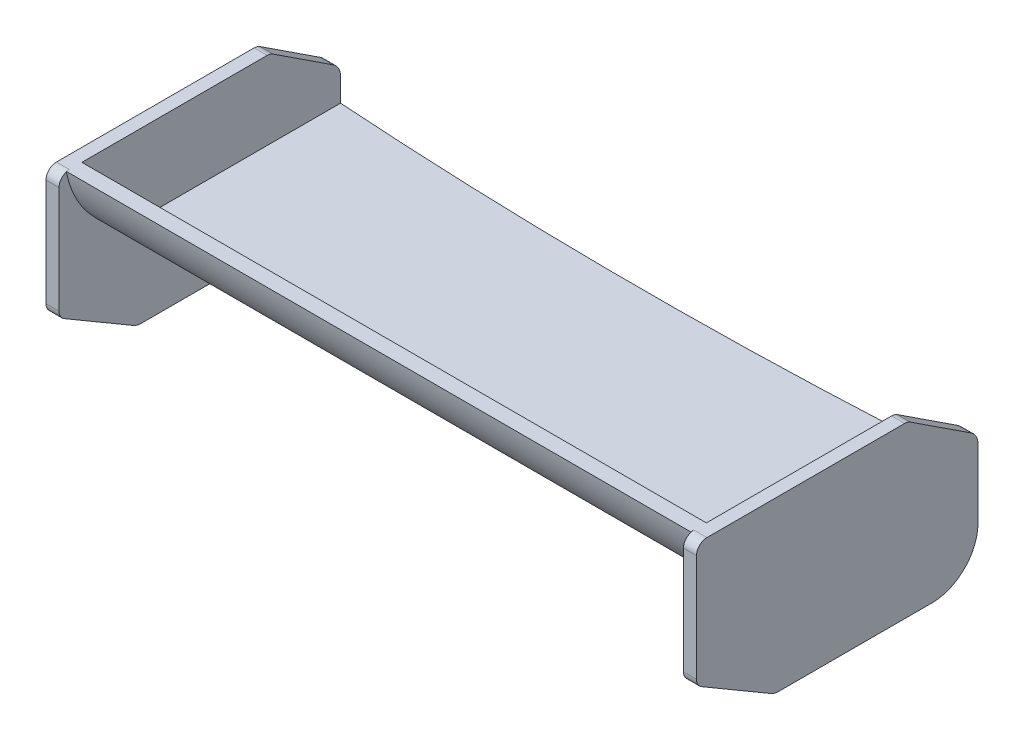
SolidWorks part; units mm, degrees
ref_plane "Alzado" through (0, 0, 0) normal (0, 0, 1) x (1, 0, 0)
ref_plane "Planta" through (0, 0, 0) normal (0, 1, 0) x (1, 0, 0)
ref_plane "Vista lateral" through (0, 0, 0) normal (1, 0, 0) x (0, 0, -1)
sketch "Croquis3" plane through (0, 0, 0) normal (0, 1, 0) x (1, 0, 0)
  line L1 (-60, 0) -> (-60, -35.6)
  line L2 (60, 0) -> (60, -35.6)
  line L3 (-60, -17.8) -> (60, -17.8) construction
  arc A0 (-60, 0) -> (60, 0) centre (0, 894.1246) ccw
  arc A1 (-60, -35.6) -> (60, -35.6) centre (0, 858.5246) ccw
  point P4 (0, 0)
  dimension "D1" = 120
  dimension "D2" = 35.6
extrude "Saliente-Extruir2" add sketch "Croquis3" along normal blind 2.5
ref_plane "Plano2" through (0, 0, 0) normal (1, 0, 0) x (0, 0, -1)
sketch "Croquis6" plane through (0, 2.5, 0) normal (0, 1, 0) x (1, 0, 0)
  line L1 (0, -37.6109) -> (0, -39.1109)
  line L2 (0, -1.375) -> (0, 1.375) construction
  line L3 (-60, -37.1) -> (-60, -52.7)
  line L4 (60, -37.1) -> (60, -52.7)
  arc A1 (-60, -52.7) -> (60, -52.7) centre (0, 841.4246) ccw
  arc A2 (-60, -37.1) -> (60, -37.1) centre (0, 857.0246) ccw
  dimension "D1" = 15.6
extrude "Saliente-Extruir3" add sketch "Croquis6" along normal blind 15 separate body contours A2 L3 A1 L4 region at (0, 2.5, 46.2409)
sketch "Croquis7" plane through (60, 0, 0) normal (1, 0, 0) x (0, 0, -1)
  line L0 (-52.7, 17.5) -> (-49.7, 17.5)
  line L1 (-37.1, 17.5) -> (-52.7, 17.5) construction
  line L2 (-37.1, 2.5) -> (-40.1, 2.5)
  line L3 (-37.1, 2.5) -> (-52.7, 2.5) construction
  line L4 (-49.7, 17.5) -> (-37.1, 17.5)
  line L5 (-37.1, 17.5) -> (-37.1, 2.5)
  line L6 (-52.7, 17.5) -> (-52.7, 2.5)
  line L7 (-52.7, 17.5) -> (-52.7, 2.5) construction
  line L8 (-52.7, 2.5) -> (-40.1, 2.5)
  arc A0 (-49.7, 17.5) -> (-37.1, 2.5) centre (-29.8357, 21.394) ccw
  arc A1 (-52.7, 17.5) -> (-40.1, 2.5) centre (-33.0482, 21.2155) ccw
  line M5 (-52.7, 2.5) -> (-37.1, 2.5)
  line M6 (-37.1, 2.5) -> (-37.1, 17.5)
  line M7 (-37.1, 17.5) -> (-52.7, 17.5)
  line M8 (-52.7, 17.5) -> (-52.7, 2.5)
extrude "Cortar-Extruir1" cut sketch "Croquis7" against normal blind 135 contours A0 M7 M6 | A1 M8 M5 region at (60, 6.4714, 49.2339) region at (60, 11.6756, 42.0524)
sketch "Croquis8" plane through (0, 17.5, 0) normal (0, 1, 0) x (1, 0, 0)
  line L0 (-60, -52.7) -> (60, -52.7)
  arc A0 (-60, -52.7) -> (60, -52.7) centre (0, 841.4246) ccw
extrude "Cortar-Extruir2" cut sketch "Croquis8" against normal blind 135
sketch "Croquis9" plane through (60, 0, 0) normal (1, 0, 0) x (0, 0, -1)
  line L1 (-54.0966, 15.5) -> (-54.0966, -5.0785)
  line L9 (-52.0966, 17.5) -> (-14.0966, 17.5)
  line L10 (0, 7.038) -> (0, -6.1372)
  line L12 (-13.0009, 17.1732) -> (-1.3565, 9.5477)
  line L14 (-38.3051, -15) -> (-8.8406, -15)
  line L15 (-53.1076, -6.8041) -> (-39.8217, -14.5884)
  arc A0 (-14.0966, 17.5) -> (-13.0009, 17.1732) centre (-14.0966, 15.5) cw
  arc A1 (-54.0966, 15.5) -> (-52.0966, 17.5) centre (-52.0966, 15.5) cw
  arc A3 (-38.3051, -15) -> (-39.8217, -14.5884) centre (-38.3051, -12) cw
  arc A4 (0, 7.038) -> (-1.3565, 9.5477) centre (-3, 7.038) ccw
  arc A6 (0, -6.1372) -> (-8.8851, -15) centre (-8.8629, -6.1372) cw
  arc A7 (-53.1076, -6.8041) -> (-54.0966, -5.0785) centre (-52.0966, -5.0785) cw
  point P7 (-35.6, 1.25)
  point P13 (0, 0.4504)
  point P20 (-52.7, 17.5)
  line M15 (-35.6, 0) -> (0, 0)
  line M16 (0, 0) -> (0, 2.5)
  line M17 (0, 2.5) -> (-35.6, 2.5)
  line M18 (-35.6, 2.5) -> (-35.6, 0)
  dimension "D1" = 2
  dimension "D2" = 3
  dimension "D3" = 2
extrude "Saliente-Extruir4" add sketch "Croquis9" along normal blind 2.5 contours A7 L15 A3 L14 A6 L10 A4 L12 A0 L9 A1 M15 M18 M17 | M18 M15 M16 M17 region at (60, 16.468, 53.0646) region at (60, 1.25, 17.8)
mirror "Simetría1" about plane through (0, 0, 0) normal (1, 0, 0) of "Saliente-Extruir4"
sketch "Croquis10" plane through (0, 2.5, 0) normal (0, 1, 0) x (1, 0, 0)
  line L2 (0, -2.0109) -> (0.75, -2.0106)
  line L3 (0.75, -2.0106) -> (0.75, -37.6106)
  line L4 (-0.75, -2.0106) -> (-0.75, -37.6106)
  line L7 (-33.55, -1.3826) -> (-33.55, -36.9826)
  line L8 (-32.05, -1.4376) -> (-32.05, -37.0376)
  line L11 (32.05, -1.4376) -> (32.05, -37.0376)
  line L12 (33.55, -1.3826) -> (33.55, -36.9826)
  arc A0 (-0.75, -2.0106) -> (0.75, -2.0106) centre (0, 894.1246) ccw
  arc A1 (-33.55, -1.3826) -> (-32.05, -1.4376) centre (0, 894.1246) ccw
  arc A2 (32.05, -1.4376) -> (33.55, -1.3826) centre (0, 894.1246) ccw
  arc A4 (-33.55, -36.9826) -> (-32.05, -37.0376) centre (0, 858.5246) ccw
  arc A5 (-0.75, -37.6106) -> (0.75, -37.6106) centre (0, 858.5246) ccw
  arc A6 (32.05, -37.0376) -> (33.55, -36.9826) centre (0, 858.5246) ccw
  point P10 (0, -2.0109)
  point P16 (0, -2.0109)
  point P22 (0.75, -2.0106)
  point P26 (0, -37.6109)
  point P29 (-0.75, -2.0112)
extrude "Saliente-Extruir5" add sketch "Croquis10" against normal blind 3.5 contours L8 A4 L7 A1 | A0 L4 A5 L3 | L12 A6 L11 A2
sketch "Croquis11" plane through (0, 0, 0) normal (0, -1, 0) x (1, 0, 0)
  line L0 (-32.05, 23.6109) -> (-32.05, 22.1109)
  line L2 (32.05, 1.4376) -> (32.05, 37.0376) construction
  line L3 (-32.05, 16.1109) -> (-32.05, 14.6109)
  line L5 (-32.05, 9.9109) -> (-32.05, 8.4109)
  line L6 (32.05, 9.9109) -> (32.05, 8.4109)
  line L7 (-32.05, 23.6109) -> (32.05, 23.6109)
  line L8 (-32.05, 22.1109) -> (32.05, 22.1109)
  line L9 (32.05, 16.1109) -> (32.05, 14.6109)
  line L10 (-32.05, 16.1109) -> (32.05, 16.1109)
  line L11 (32.05, 23.6109) -> (32.05, 22.1109)
  line L12 (-32.05, 14.6109) -> (32.05, 14.6109)
  line L13 (32.05, 1.4376) -> (32.05, 37.0376) construction
  line L14 (-60, 29.8109) -> (60, 29.8109)
  line L15 (-32.05, 9.9109) -> (32.05, 9.9109)
  line L16 (60, 38.3051) -> (60, 8.8406) construction
  line L17 (-32.05, 8.4109) -> (32.05, 8.4109)
  line L20 (-60, 28.3109) -> (60, 28.3109)
  line L21 (-60, 29.8109) -> (-60, 28.3109)
  line L22 (60, 29.8109) -> (60, 28.1162)
  point P5 (0, 29.8109)
  point P12 (0, 29.8109)
  point P13 (0, 28.3109)
  point P16 (0, 28.3109)
  point P28 (0, 16.1109)
  point P34 (0, 14.6109)
  point P38 (0, 9.9109)
  point P41 (0, 8.4109)
  line M27 (-0.75, 2.0106) -> (-0.75, 37.6106)
  line M29 (-32.05, 37.0376) -> (-32.05, 1.4376)
extrude "Saliente-Extruir6" add sketch "Croquis11" along normal blind 1 contours L12 L10 M29 M27 | L12 L9 L10 M27 | L8 L7 M29 M27 | L11 L7 L8 M27 | L17 L6 L15 L5 region at (-16.4, 0, 22.8609) region at (15.65, 0, 22.8609) region at (-16.4, 0, 15.3609) region at (15.65, 0, 15.3609)
sketch "Croquis12" plane through (0, 0, 0) normal (0, -1, 0) x (1, 0, 0)
  line L4 (-32.05, 9.9109) -> (-32.05, 8.4109)
  line L5 (-60, 29.8109) -> (-60, 28.3109)
  line L7 (-60, 28.3109) -> (60, 28.3109)
  line L8 (60, 35.6) -> (60, 0) construction
  line L9 (-60, 29.8109) -> (60, 29.8109)
  line L10 (60, 38.3051) -> (60, 8.8406) construction
  line L13 (60, 29.8109) -> (60, 28.3109)
  point P21 (-0.75, 28.3109)
  point P25 (-0.75, 29.8109)
extrude "Saliente-Extruir7" add sketch "Croquis12" along normal blind 1 contours L9 L13 L7 L5
sketch "Croquis13" plane through (0, 0, 0) normal (0, -1, 0) x (1, 0, 0)
  line L0 (0, 37.6109) -> (0, 2.4457)
  line L2 (33.55, 13.0109) -> (33.55, 11.5109)
  line L3 (33.55, 1.3826) -> (33.55, 28.3109) construction
  line L4 (33.55, 13.0109) -> (60, 13.0109)
  line L5 (60, 28.3109) -> (60, 0) construction
  line L6 (33.55, 11.5109) -> (60, 11.5109)
  line L7 (60, 38.3051) -> (60, 8.8406) construction
  line L8 (60, 13.0109) -> (60, 11.5109)
  line L9 (-60, 13.0109) -> (-60, 11.5109)
  line L10 (-33.55, 13.0109) -> (-33.55, 11.5109)
  line L11 (-33.55, 11.5109) -> (-60, 11.5109)
  line L12 (-33.55, 13.0109) -> (-60, 13.0109)
  arc A0 (0.75, 37.6106) -> (-0.75, 37.6106) centre (0, -858.5246) ccw construction
  point P11 (33.55, 12.2609)
  point P23 (-33.55, 12.2609)
extrude "Saliente-Extruir8" add sketch "Croquis13" along normal blind 1 contours L11 L9 L12 L10 | L4 L8 L6 L2
sketch "Croquis14" plane through (0, 0, 0) normal (0, -1, 0) x (1, 0, 0)
  line L0 (-50.7801, 28.3109) -> (-49.2801, 28.3109)
  line L1 (50.7801, 13.0109) -> (49.2801, 13.0109)
  line L2 (-50.7801, 13.0109) -> (-49.2801, 13.0109)
  line L3 (-33.55, 13.0109) -> (-60, 13.0109) construction
  line L4 (-60, 28.3109) -> (-33.55, 28.3109) construction
  line L5 (-49.2801, 28.3109) -> (-49.2801, 13.0109)
  line L6 (-33.55, 13.0109) -> (-60, 13.0109) construction
  line L7 (-50.7801, 28.3109) -> (-50.7801, 13.0109)
  line L8 (0, 37.6109) -> (0, 2.0109) construction
  line L9 (50.7801, 28.3109) -> (49.2801, 28.3109)
  line L10 (50.7801, 28.3109) -> (50.7801, 13.0109)
  line L11 (49.2801, 28.3109) -> (49.2801, 13.0109)
  arc A0 (0.75, 37.6106) -> (-0.75, 37.6106) centre (0, -858.5246) ccw construction
  arc A1 (0.75, 2.0106) -> (-0.75, 2.0106) centre (0, -894.1246) ccw construction
  point P12 (-50.0301, 28.3109)
extrude "Saliente-Extruir9" add sketch "Croquis14" along normal blind 1
sketch "Croquis15" plane through (0, 0, 0) normal (0, -1, 0) x (1, 0, 0)
  line L0 (-22.8, 19.1109) -> (-21.3, 19.1109)
  line L1 (-12.6464, 19.1109) -> (-11.1464, 19.1109)
  line L2 (-12.6464, 28.3109) -> (-12.6464, 9.9109)
  line L3 (-32.05, 9.9109) -> (-0.75, 9.9109) construction
  line L4 (-21.3, 28.3109) -> (-21.3, 9.9109)
  line L5 (-32.05, 9.9109) -> (-0.75, 9.9109) construction
  line L6 (-21.3, 9.9109) -> (-22.8, 9.9109)
  line L7 (-22.8, 9.9109) -> (-22.8, 28.3109)
  line L8 (-32.05, 28.3109) -> (-0.75, 28.3109) construction
  line L9 (-22.8, 28.3109) -> (-21.3, 28.3109)
  line L10 (-11.1464, 28.3109) -> (-11.1464, 9.9109)
  line L12 (-12.6464, 28.3109) -> (-11.1464, 28.3109)
  line L13 (-12.6464, 9.9109) -> (-11.1464, 9.9109)
  line L14 (0, 37.6109) -> (0, 2.0109) construction
  line L15 (12.6464, 28.3109) -> (11.1464, 28.3109)
  line L16 (11.1464, 28.3109) -> (11.1464, 9.9109)
  line L17 (12.6464, 28.3109) -> (12.6464, 9.9109)
  line L18 (12.6464, 9.9109) -> (11.1464, 9.9109)
  line L19 (21.3, 9.9109) -> (22.8, 9.9109)
  line L20 (22.8, 28.3109) -> (21.3, 28.3109)
  line L21 (22.8, 9.9109) -> (22.8, 28.3109)
  line L22 (21.3, 28.3109) -> (21.3, 9.9109)
  arc A0 (0.75, 37.6106) -> (-0.75, 37.6106) centre (0, -858.5246) ccw construction
  arc A1 (0.75, 2.0106) -> (-0.75, 2.0106) centre (0, -894.1246) ccw construction
  point P3 (-22.05, 19.1109)
  point P9 (-22.05, 19.1109)
  point P13 (-21.3, 19.1109)
  point P20 (-11.8964, 19.1109)
  point P21 (-12.6464, 19.1109)
  point P23 (-11.1464, 19.1109)
  line M10 (-0.75, 22.1109) -> (-32.05, 22.1109)
  line M12 (-32.05, 16.1109) -> (-0.75, 16.1109)
extrude "Saliente-Extruir10" add sketch "Croquis15" along normal blind 1 contours L10 L2 L1 M10 | L12 L2 L10 M10 | L10 L1 L2 M12 | L2 L13 L10 M12 | L7 L9 L4 L6 | L17 L18 L16 L15 | L21 L20 L22 L19 region at (-11.8964, 0, 20.6109) region at (-11.8964, 0, 25.2109) region at (-11.8964, 0, 13.0109) region at (-11.8964, 0, 17.6109)
sketch "Croquis18" plane through (0, 0, 0) normal (0, -1, 0) x (1, 0, 0)
  line L0 (0, 37.6109) -> (0, 2.0109) construction
  line L1 (-14.5, 14.0109) -> (14.5, 14.0109) construction
  circle A0 centre (-14.5, 14.0109) radius 2.5
  arc A1 (0.75, 37.6106) -> (-0.75, 37.6106) centre (0, -858.5246) ccw construction
  circle A2 centre (14.5, 14.0109) radius 2.5
  arc A3 (0.75, 2.0106) -> (-0.75, 2.0106) centre (0, -894.1246) ccw construction
  point P2 (0, 2.0109)
  dimension "D1" = 5
  dimension "D2" = 29
  dimension "D3" = 12
extrude "Saliente-Extruir11" add sketch "Croquis18" along normal blind 5.1
sketch "Croquis19" plane through (0, -5.1, 0) normal (0, -1, 0) x (1, 0, 0)
  circle A0 centre (-14.5, 14.0109) radius 1.3
  circle A1 centre (14.5, 14.0109) radius 1.3
  dimension "D1" = 2.6
  dimension "D2" = 2.6
extrude "Cortar-Extruir3" cut sketch "Croquis19" against normal blind 3
thread "Rosca1" pitch 0.3 method extrude profile "Perfil de rosca1" start angle 0, offset 0, length 0, pitch 0.3, diameter 2.6
ref_plane "Plano3" through (-13.2, -5.1, 14.0109) normal (0, 0, 1) x (1, 0, 0)
sketch "Perfil de rosca1" plane through (-13.2, -5.1, 14.0109) normal (0, 0, 1) x (1, 0, 0)
  line L0 (0, 0) -> (0, 0.3) construction
  line L11 (0, 0) -> (0, 0.2625)
  line L12 (0, 0.2625) -> (-0.1624, 0.1687)
  line L13 (-0.1624, 0.1687) -> (-0.1624, 0.0937)
  line L15 (-0.1624, 0.0937) -> (0, 0)
  line L17 (-0.1624, 0.1312) -> (0, 0.1312) construction
  point P2 (0, 0)
  dimension "Pitch" = 0.3
  dimension "Profile_Angle" = 60
  dimension "Profile_Land" = 0.075
  dimension "Profile_Height" = 0.1624
thread "Rosca2" pitch 0.3 method extrude profile "Perfil de rosca2" start angle 0, offset 0, length 0, pitch 0.3, diameter 2.6
ref_plane "Plano4" through (15.8, -5.1, 14.0109) normal (0, 0, 1) x (1, 0, 0)
sketch "Perfil de rosca2" plane through (15.8, -5.1, 14.0109) normal (0, 0, 1) x (1, 0, 0)
  line L0 (0, 0) -> (0, 0.3) construction
  line L11 (0, 0) -> (0, 0.2625)
  line L12 (0, 0.2625) -> (-0.1624, 0.1687)
  line L13 (-0.1624, 0.1687) -> (-0.1624, 0.0937)
  line L15 (-0.1624, 0.0937) -> (0, 0)
  line L17 (-0.1624, 0.1312) -> (0, 0.1312) construction
  point P2 (0, 0)
  dimension "Pitch" = 0.3
  dimension "Profile_Angle" = 60
  dimension "Profile_Land" = 0.075
  dimension "Profile_Height" = 0.1624
